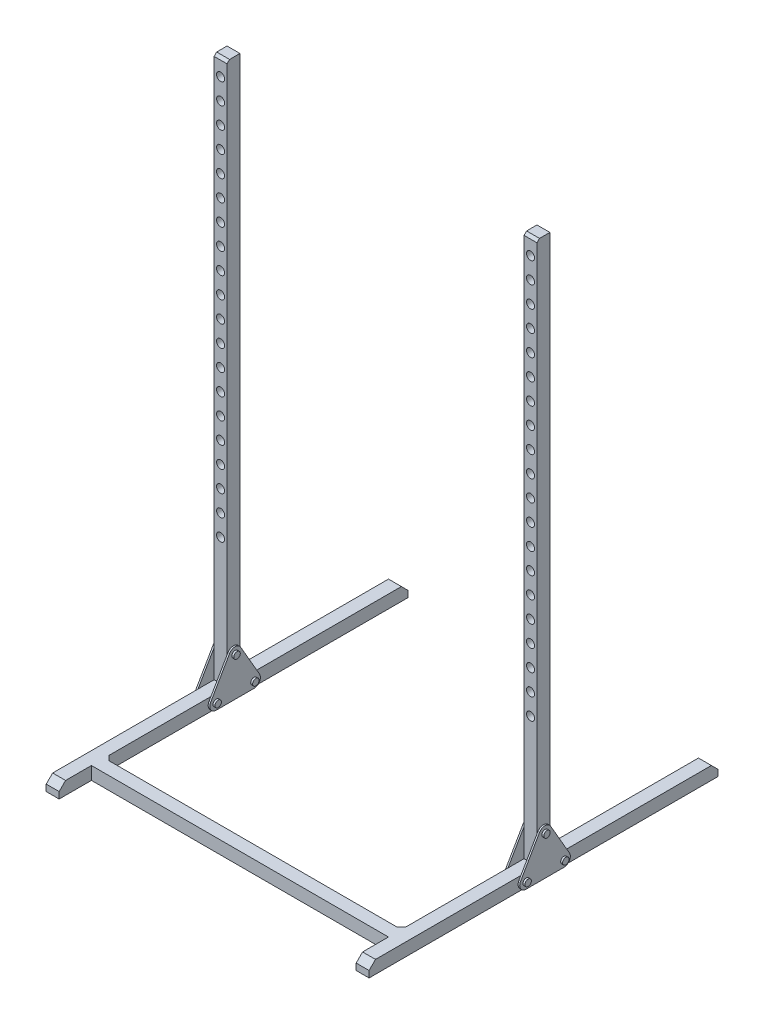
SolidWorks part; units mm, degrees
ref_plane "Front Plane" through (0, 0, 0) normal (0, 0, 1) x (1, 0, 0)
ref_plane "Top Plane" through (0, 0, 0) normal (0, 1, 0) x (1, 0, 0)
ref_plane "Right Plane" through (0, 0, 0) normal (1, 0, 0) x (0, 0, -1)
sketch "Sketch1" plane through (0, 0, 0) normal (0, 0, 1) x (1, 0, 0)
  line L1 (-25.4, 25.4) -> (25.4, 25.4)
  line L2 (-25.4, 25.4) -> (-25.4, -25.4)
  line L3 (-25.4, -25.4) -> (25.4, -25.4)
  line L4 (25.4, 25.4) -> (25.4, -25.4)
  line L5 (-25.4, 25.4) -> (25.4, -25.4) construction
  line L6 (-25.4, -25.4) -> (25.4, 25.4) construction
  point P0 (0, 0)
  dimension "D1" = 50.8
  dimension "D2" = 50.8
extrude "Boss-Extrude1" add sketch "Sketch1" along normal blind 1371.6
sketch "Sketch2" plane through (25.4, 0, 0) normal (1, 0, 0) x (0, 0, -1)
  line L0 (-1371.6, -25.4) -> (0, -25.4) construction
  line L1 (-1244.6284, 25.4) -> (-1193.8284, 25.4)
  line L2 (-1244.6284, 25.4) -> (-1244.6284, -25.4)
  line L3 (-1244.6284, -25.4) -> (-1193.8284, -25.4)
  line L4 (-1193.8284, 25.4) -> (-1193.8284, -25.4)
  line L5 (-1244.6284, 25.4) -> (-1193.8284, -25.4) construction
  line L6 (-1244.6284, -25.4) -> (-1193.8284, 25.4) construction
  point P0 (-1219.2284, 0)
  dimension "D1" = 50.8
extrude "Boss-Extrude2" add sketch "Sketch2" along normal blind 1168.4
ref_plane "Plane1" through (609.6, 0, 0) normal (1, 0, 0) x (0, 0, -1)
mirror "Mirror1" about plane through (609.6, 0, 0) normal (1, 0, 0) of "Boss-Extrude1"
sketch "Sketch3" plane through (0, 25.4, 0) normal (0, 1, 0) x (1, 0, 0)
  line L0 (25.4, -1193.8284) -> (25.4, 0) construction
  line L1 (-25.4, -660.4) -> (25.4, -660.4)
  line L2 (-25.4, -660.4) -> (-25.4, -711.2)
  line L3 (-25.4, -711.2) -> (25.4, -711.2)
  line L4 (25.4, -660.4) -> (25.4, -711.2)
  line L5 (-25.4, -660.4) -> (25.4, -711.2) construction
  line L6 (-25.4, -711.2) -> (25.4, -660.4) construction
  point P0 (0, -685.8)
  dimension "D1" = 50.8
  dimension "D2" = 660.4
extrude "Boss-Extrude3" add sketch "Sketch3" along normal blind 2133.6
sketch "Sketch4" plane through (-25.4, 0, 0) normal (-1, 0, 0) x (0, 0, 1)
  line L0 (567.6847, -25.4) -> (685.8, 179.1817)
  line L1 (1371.6, -25.4) -> (0, -25.4) construction
  line L2 (685.8, 179.1817) -> (803.9153, -25.4)
  line L3 (803.9153, -25.4) -> (567.6847, -25.4)
  line L5 (660.4, 179.1817) -> (711.2, 179.1817)
  line L6 (660.4, 2159) -> (660.4, 25.4) construction
  line L7 (711.2, 2159) -> (711.2, 25.4) construction
  point P8 (685.8, 179.1817)
  line M5 (0, -25.4) -> (1371.6, -25.4)
  line M7 (1371.6, 25.4) -> (711.2, 25.4)
  line M8 (711.2, 25.4) -> (711.2, 2159)
  line M10 (660.4, 2159) -> (660.4, 25.4)
  line M11 (660.4, 25.4) -> (0, 25.4)
extrude "Boss-Extrude4" add sketch "Sketch4" along normal blind 6.35 contours L2 L0 M10 M11 M5 M7 M8 | L0 M11 M10 | L2 M8 M7 region at (-25.4, 35.0273, 685.8) region at (-25.4, 61.9959, 639.2714) region at (-25.4, 61.9959, 732.3286)
fillet "Fillet1" radius 25.4 3 edges at (-28.575, -25.4, 567.6847) (-28.575, -25.4, 803.9153) (-28.575, 179.1817, 685.8)
ref_plane "Plane2" through (0, 0, 0) normal (1, 0, 0) x (0, 0, -1)
mirror "Mirror2" about plane through (0, 0, 0) normal (1, 0, 0) of "Boss-Extrude4"
fillet "Fillet2" radius 25.4 3 edges at (28.575, -25.4, 803.9153) (28.575, -25.4, 567.6847) (28.575, 179.1817, 685.8)
mirror "Mirror4" about plane through (609.6, 0, 0) normal (1, 0, 0) of "Mirror2", "Boss-Extrude3", "Boss-Extrude4"
fillet "Fillet3" radius 25.4 6 edges at (1247.775, -25.4, 803.9153) (1190.625, -25.4, 803.9153) (1190.625, -25.4, 567.6847) (1247.775, -25.4, 567.6847) (1247.775, 179.1817, 685.8) (1190.625, 179.1817, 685.8)
chamfer "Chamfer1" distance 25.24 angle 45 4 edges at (1219.2, 25.4, 1371.6) (0, 25.4, 1371.6) (0, 25.4, 0) (1219.2, 25.4, 0)
chamfer "Chamfer2" distance 17.62 angle 45 2 edges at (25.4, 0, 1193.8284) (1193.8, 0, 1193.8284)
sketch "Sketch7" plane through (0, 0, 660.4) normal (0, 0, -1) x (-1, 0, 0)
  line L0 (-25.4, 2159) -> (25.4, 2159) construction
  circle A0 centre (0, 2092.325) radius 15.875
  dimension "D1" = 31.75
  dimension "D2" = 50.8
extrude "Cut-Extrude1" cut sketch "Sketch7" against normal through all
pattern_linear "LPattern1" count 20 spacing 82.55 along (0, -1, 0) of "Cut-Extrude1"
mirror "Mirror5" about plane through (609.6, 0, 0) normal (1, 0, 0) of "LPattern1"
sketch "Sketch8" plane through (-31.75, 0, 0) normal (-1, 0, 0) x (0, 0, 1)
  circle A0 centre (685.8, 128.3817) radius 12.7
  circle A1 centre (611.6788, 0) radius 12.7
  circle A2 centre (759.9212, 0) radius 12.7
  dimension "D1" = 25.4
  dimension "D2" = 25.4
  dimension "D3" = 25.4
extrude "Boss-Extrude5" add sketch "Sketch8" along normal blind 7.62
mirror "Mirror6" about plane through (0, 0, 0) normal (1, 0, 0) of "Boss-Extrude5"
mirror "Mirror7" about plane through (609.6, 0, 0) normal (1, 0, 0) of "Mirror6"
chamfer "Chamfer3" distance 10 angle 45 2 edges at (0, 2159, 711.2) (1219.2, 2159, 711.2)
